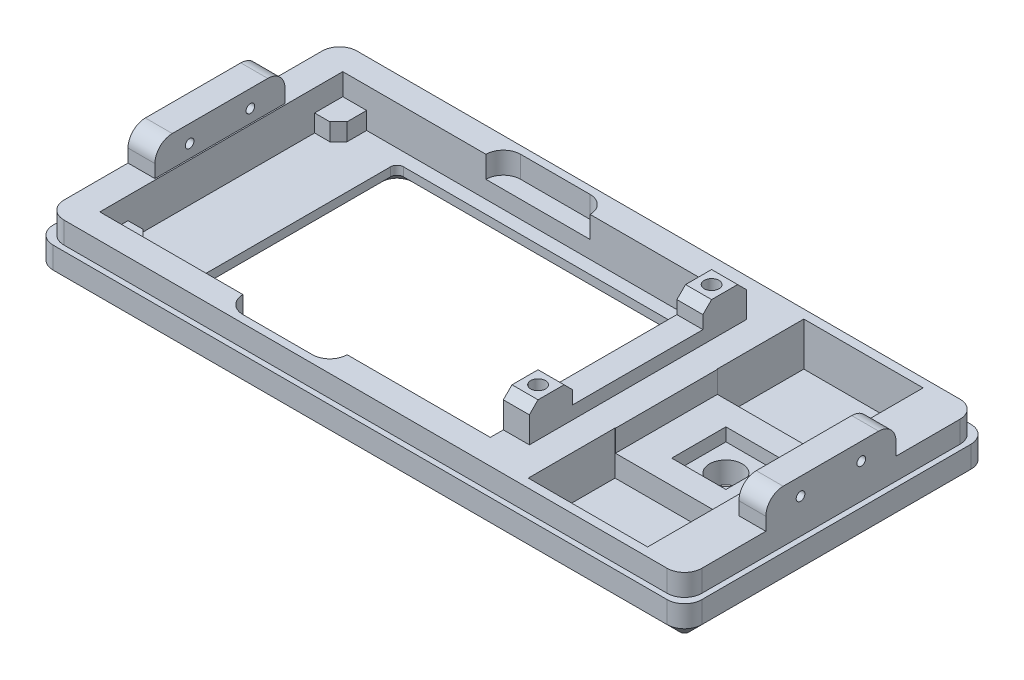
SolidWorks part; units mm, degrees
ref_plane "Front Plane" through (0, 0, 0) normal (0, 0, 1) x (1, 0, 0)
ref_plane "Top Plane" through (0, 0, 0) normal (0, 1, 0) x (1, 0, 0)
ref_plane "Right Plane" through (0, 0, 0) normal (1, 0, 0) x (0, 0, -1)
sketch "Sketch1" plane through (0, 0, 0) normal (0, 1, 0) x (1, 0, 0)
  line L1 (-74.75, 35) -> (74.75, 35)
  line L2 (-74.75, 35) -> (-74.75, -35)
  line L3 (-74.75, -35) -> (74.75, -35)
  line L4 (74.75, 35) -> (74.75, -35)
  line L5 (-74.75, 35) -> (74.75, -35) construction
  line L6 (-74.75, -35) -> (74.75, 35) construction
  point P0 (0, 0)
  dimension "D1" = 70
  dimension "D2" = 149.5
extrude "Boss-Extrude1" add sketch "Sketch1" along normal blind 8
fillet "Fillet1" radius 4 4 edges at (-74.75, 4, -35) (-74.75, 4, 35) (74.75, 4, -35) (74.75, 4, 35)
sketch "Sketch6" plane through (0, 8, 0) normal (0, 1, 0) x (1, 0, 0)
  line L1 (-73.5, 33.75) -> (73.5, 33.75)
  line L2 (-73.5, 33.75) -> (-73.5, -33.75)
  line L3 (-73.5, -33.75) -> (73.5, -33.75)
  line L4 (73.5, 33.75) -> (73.5, -33.75)
  line L5 (-73.5, 33.75) -> (73.5, -33.75) construction
  line L6 (-73.5, -33.75) -> (73.5, 33.75) construction
  point P0 (0, 0)
  dimension "D1" = 67.5
  dimension "D2" = 147
extrude "Boss-Extrude3" add sketch "Sketch6" along normal blind 5
fillet "Fillet2" radius 4 4 edges at (-73.5, 10.5, 33.75) (73.5, 10.5, 33.75) (73.5, 10.5, -33.75) (-73.5, 10.5, -33.75)
sketch "Sketch7" plane through (0, 13, 0) normal (0, 1, 0) x (1, 0, 0)
  line L0 (-73.5, 0) -> (0, 0) construction
  line L1 (-73.5, 29.75) -> (-73.5, -29.75) construction
  line L2 (0, 0) -> (0, 33.75) construction
  line L3 (69.5, 33.75) -> (-69.5, 33.75) construction
  line L4 (-73.5, -15) -> (-73.5, 15)
  line L5 (-73.5, 29.75) -> (-73.5, -29.75) construction
  line L6 (-73.5, 15) -> (-67.2945, 15)
  line L7 (-67.2945, 15) -> (-67.2945, -15)
  line L8 (-73.5, -15) -> (-67.2945, -15)
  line L9 (73.5, 15) -> (67.2945, 15)
  line L10 (73.5, -15) -> (73.5, 15)
  line L11 (73.5, -15) -> (67.2945, -15)
  line L12 (67.2945, 15) -> (67.2945, -15)
  point P14 (-67.2945, 0)
  dimension "D1" = 15
extrude "Boss-Extrude4" add sketch "Sketch7" along normal blind 7
sketch "Sketch8" plane through (-73.5, 0, 0) normal (-1, 0, 0) x (0, 0, 1)
  line L0 (0, 20) -> (0, 0) construction
  line L1 (-15, 20) -> (15, 20) construction
  circle A0 centre (-7, 16) radius 1
  circle A1 centre (7, 16) radius 1
  dimension "D1" = 2
  dimension "D2" = 4
  dimension "D3" = 14
extrude "Cut-Extrude3" cut sketch "Sketch8" against normal through all
fillet "Fillet5" radius 4 4 edges at (70.3973, 20, 15) (70.3973, 20, -15) (-70.3973, 20, 15) (-70.3973, 20, -15)
sketch "Sketch9" plane through (0, 13, 0) normal (0, 1, 0) x (1, 0, 0)
  line L0 (0, 0) -> (-67.2945, 0) construction
  line L1 (-67.2945, -15) -> (-67.2945, 15) construction
  line L3 (-67, 28) -> (23, 28)
  line L4 (-67, 28) -> (-67, -28)
  line L5 (-67, -28) -> (23, -28)
  line L6 (23, 28) -> (23, -28)
  line L7 (-67, 28) -> (23, -28) construction
  line L8 (-67, -28) -> (23, 28) construction
  point P5 (-22, 0)
  dimension "D1" = 90
  dimension "D2" = 56
  dimension "D3" = 22
extrude "Cut-Extrude4" cut sketch "Sketch9" against normal blind 5
sketch "Sketch10" plane through (0, 8, 0) normal (0, 1, 0) x (1, 0, 0)
  line L0 (-67, 28) -> (23, -28) construction
  line L1 (23, 28) -> (-67, -28) construction
  line L3 (-61.5, 28) -> (17.5, 28)
  line L4 (-61.5, 28) -> (-61.5, -28)
  line L5 (-61.5, -28) -> (17.5, -28)
  line L6 (17.5, 28) -> (17.5, -28)
  line L7 (-61.5, 28) -> (17.5, -28) construction
  line L8 (-61.5, -28) -> (17.5, 28) construction
  point P8 (-22, 0)
  dimension "D1" = 79
  dimension "D2" = 56
extrude "Cut-Extrude5" cut sketch "Sketch10" against normal blind 4
sketch "Sketch11" plane through (0, 4, 0) normal (0, 1, 0) x (1, 0, 0)
  line L0 (-61.5, 0) -> (17.5, 0) construction
  line L1 (-61.5, 28) -> (-61.5, -28) construction
  line L2 (17.5, -28) -> (17.5, 28) construction
  line L4 (-51.5, 25) -> (14.5, 25)
  line L5 (-51.5, 25) -> (-51.5, -25)
  line L6 (-51.5, -25) -> (14.5, -25)
  line L7 (14.5, 25) -> (14.5, -25)
  line L8 (-51.5, 25) -> (14.5, -25) construction
  line L9 (-51.5, -25) -> (14.5, 25) construction
  point P6 (-18.5, 0)
  dimension "D1" = 66
  dimension "D2" = 50
  dimension "D3" = 3
extrude "Cut-Extrude6" cut sketch "Sketch11" against normal through all
sketch "Sketch13" plane through (0, 13, 0) normal (0, 1, 0) x (1, 0, 0)
  line L0 (23, 0) -> (67.2945, 0) construction
  line L1 (23, -28) -> (23, 28) construction
  line L2 (67.2945, 11) -> (67.2945, -11) construction
  line L3 (23, -25) -> (23, 25)
  line L4 (23, 25) -> (29, 25)
  line L5 (29, 25) -> (29, -25)
  line L6 (23, -25) -> (29, -25)
  point P10 (29, 0)
  dimension "D1" = 25
  dimension "D2" = 6
extrude "Boss-Extrude5" add sketch "Sketch13" along normal blind 8
sketch "Sketch14" plane through (0, 21, 0) normal (0, 1, 0) x (1, 0, 0)
  line L0 (23, 0) -> (29, 0) construction
  line L1 (23, 25) -> (23, -25) construction
  line L2 (29, -25) -> (29, 25) construction
  circle A0 centre (26, 20) radius 1.6928
  circle A1 centre (26, -20) radius 1.6928
  dimension "D1" = 3
  dimension "D2" = 20
extrude "Cut-Extrude7" cut sketch "Sketch14" against normal through all
sketch "Sketch15" plane through (0, 21, 0) normal (0, 1, 0) x (1, 0, 0)
  line L0 (23, 0) -> (29, 0) construction
  line L1 (23, 25) -> (23, -25) construction
  line L2 (29, -25) -> (29, 25) construction
  line L3 (23, -15) -> (23, 15)
  line L4 (23, -28) -> (23, 28) construction
  line L5 (23, 15) -> (29, 15)
  line L6 (29, -25) -> (29, 25) construction
  line L7 (29, 15) -> (29, -15)
  line L8 (23, -15) -> (29, -15)
  dimension "D1" = 15
extrude "Cut-Extrude8" cut sketch "Sketch15" against normal blind 5
chamfer "Chamfer2" distance 2 angle 45 2 edges at (26, 0, 18.3072) (26, 0, -18.3072)
sketch "Sketch16" plane through (0, 13, 0) normal (0, 1, 0) x (1, 0, 0)
  line L0 (0, 0) -> (67.2945, 0) construction
  line L1 (67.2945, 11) -> (67.2945, -11) construction
  circle A0 centre (49.2945, 0) radius 3.75
  dimension "D1" = 7.5
  dimension "D2" = 18
extrude "Cut-Extrude9" cut sketch "Sketch16" against normal through all
sketch "Sketch17" plane through (0, 13, 0) normal (0, 1, 0) x (1, 0, 0)
  line L1 (43.0445, 6.25) -> (55.5445, 6.25)
  line L2 (43.0445, 6.25) -> (43.0445, -6.25)
  line L3 (43.0445, -6.25) -> (55.5445, -6.25)
  line L4 (55.5445, 6.25) -> (55.5445, -6.25)
  line L5 (43.0445, 6.25) -> (55.5445, -6.25) construction
  line L6 (43.0445, -6.25) -> (55.5445, 6.25) construction
  point P0 (49.2945, 0)
  dimension "D1" = 12.5
  dimension "D2" = 12.5
extrude "Cut-Extrude10" cut sketch "Sketch17" against normal blind 8
sketch "Sketch20" plane through (0, 13, 0) normal (0, 1, 0) x (1, 0, 0)
  line L0 (-67.2945, 0) -> (67.2945, 0) construction
  line L1 (-67.2945, -11) -> (-67.2945, 11) construction
  line L2 (67.2945, 11) -> (67.2945, -11) construction
  line L3 (-22, 28) -> (-22, 33.75) construction
  line L4 (23, 28) -> (-67, 28) construction
  line L5 (69.5, 33.75) -> (-69.5, 33.75) construction
  line L6 (-10, 28) -> (-34, 28)
  line L7 (-34, 28) -> (-34, 32)
  line L8 (-34, 32) -> (-10, 32)
  line L9 (-10, 28) -> (-10, 32)
  line L10 (-10, -28) -> (-10, -32)
  line L11 (-34, -32) -> (-10, -32)
  line L12 (-34, -28) -> (-34, -32)
  line L13 (-10, -28) -> (-34, -28)
  point P17 (-22, 32)
  dimension "D1" = 12
  dimension "D2" = 4
extrude "Cut-Extrude12" cut sketch "Sketch20" against normal blind 5
fillet "Fillet6" radius 4 4 edges at (-34, 10.5, 32) (-10, 10.5, 32) (-10, 10.5, -32) (-34, 10.5, -32)
chamfer "Chamfer3" distance 2 angle 45 4 edges at (26, 21, 15) (26, 21, -15) (26, 21, -25) (26, 21, 25)
sketch "Sketch23" plane through (0, 8, 0) normal (0, 1, 0) x (1, 0, 0)
  line L0 (-61.5, 0) -> (-67, 0) construction
  line L1 (-61.5, 28) -> (-61.5, -28) construction
  line L2 (-67, 28) -> (-67, -28) construction
  line L3 (-61.5, -21.5) -> (-61.5, 21.5)
  line L4 (-61.5, 28) -> (-61.5, -28) construction
  line L5 (-61.5, 21.5) -> (-67, 21.5)
  line L6 (-67, 21.5) -> (-67, -21.5)
  line L7 (-61.5, -21.5) -> (-67, -21.5)
  line L8 (-22, -28) -> (-22, -10.1702) construction
  line L9 (-10, -28) -> (-34, -28) construction
  line L10 (17.5, 21.5) -> (23, 21.5)
  line L11 (17.5, -21.5) -> (17.5, 21.5)
  line L12 (17.5, -21.5) -> (23, -21.5)
  line L13 (23, 21.5) -> (23, -21.5)
  point P12 (-67, 0)
  dimension "D1" = 21.5
  dimension "D2" = 5.5
extrude "Cut-Extrude15" cut sketch "Sketch23" against normal blind 4
fillet "Fillet7" radius 1.5 4 edges at (14.5, 2, -25) (14.5, 2, 25) (-51.5, 2, 25) (-51.5, 2, -25)
chamfer "Chamfer6" distance 2 angle 45 4 edges at (-61.5, 6, 21.5) (-61.5, 6, -21.5) (17.5, 6, 21.5) (17.5, 6, -21.5)
sketch "Sketch26" plane through (0, 13, 0) normal (0, 1, 0) x (1, 0, 0)
  line L0 (-69.5, -33.75) -> (69.5, -33.75) construction
  line L1 (35.5, -11.75) -> (63, -11.75)
  line L2 (35.5, -11.75) -> (35.5, -31.75)
  line L3 (35.5, -31.75) -> (63, -31.75)
  line L4 (63, -11.75) -> (63, -31.75)
  line L5 (35.5, -11.75) -> (63, -31.75) construction
  line L6 (35.5, -31.75) -> (63, -11.75) construction
  line L7 (73.5, -29.75) -> (73.5, -15) construction
  line L8 (0, 0) -> (16.2431, 0) construction
  line L9 (35.5, 31.75) -> (63, 31.75)
  line L10 (63, 11.75) -> (63, 31.75)
  line L11 (35.5, 11.75) -> (63, 11.75)
  line L12 (35.5, 11.75) -> (35.5, 31.75)
  point P0 (49.25, -21.75)
  dimension "D1" = 20
  dimension "D2" = 27.5
  dimension "D3" = 12
  dimension "D4" = 10.5
extrude "Cut-Extrude16" cut sketch "Sketch26" against normal blind 10
sketch "Sketch27" plane through (0, 13, 0) normal (0, 1, 0) x (1, 0, 0)
  line L0 (63, -31.75) -> (63, -11.75) construction
  line L1 (35.5891, 14.4188) -> (63, 14.4188)
  line L2 (35.5891, 14.4188) -> (35.5891, -14.4188)
  line L3 (35.5891, -14.4188) -> (63, -14.4188)
  line L4 (63, 14.4188) -> (63, -14.4188)
  line L5 (35.5891, 14.4188) -> (63, -14.4188) construction
  line L6 (35.5891, -14.4188) -> (63, 14.4188) construction
  point P0 (49.2945, 0)
extrude "Cut-Extrude17" cut sketch "Sketch27" against normal blind 5
chamfer "Chamfer7" distance 3 angle 45 8 edges at (0, 0, 35) (73.5784, 0, 33.8284) (-73.5784, 0, 33.8284) (74.75, 0, 0) (-74.75, 0, 0) (73.5784, 0, -33.8284) (-73.5784, 0, -33.8284) (0, 0, -35)
chamfer "Chamfer8" distance 2 angle 45 8 edges at (14.5, 0, 0) (14.0607, 0, -24.5607) (14.0607, 0, 24.5607) (-18.5, 0, -25) (-18.5, 0, 25) (-51.0607, 0, -24.5607) (-51.0607, 0, 24.5607) (-51.5, 0, 0)
